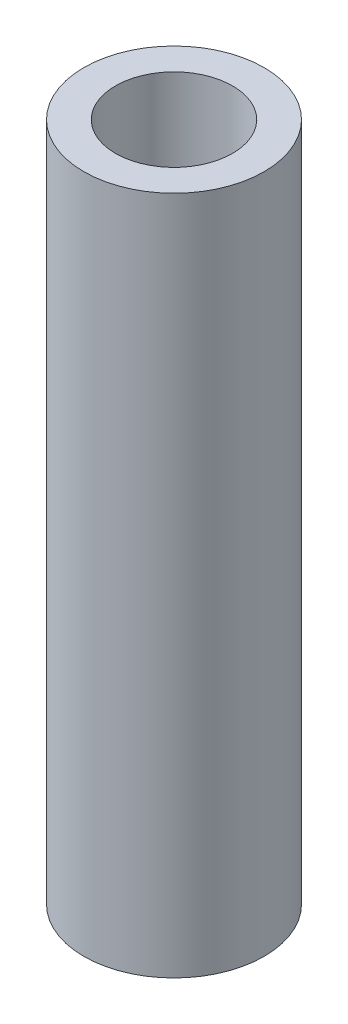
SolidWorks part; units mm, degrees
material "ABS"
ref_plane "Front Plane" through (0, 0, 0) normal (0, 0, 1) x (1, 0, 0)
ref_plane "Top Plane" through (0, 0, 0) normal (0, 1, 0) x (1, 0, 0)
ref_plane "Right Plane" through (0, 0, 0) normal (1, 0, 0) x (0, 0, -1)
sketch "Sketch1" plane through (0, 0, 0) normal (0, 1, 0) x (1, 0, 0)
  circle A0 centre (0, 0) radius 18.5
  circle A1 centre (0, 0) radius 28.5
  dimension "D1" = 37
  dimension "D2" = 57
extrude "Boss-Extrude1" add sketch "Sketch1" along normal blind 214.8
sketch "Sketch2" plane through (0, 0, 0) normal (1, 0, 0) x (0, 0, -1)
  line L0 (18.5, 214.8) -> (-18.5, 214.8) construction
  circle A0 centre (0, 150.1) radius 12.53
  circle A1 centre (0, 90.1) radius 12.53
  circle A2 centre (0, 30.1) radius 12.53
  dimension "D1" = 25.06
  dimension "D2" = 25.06
  dimension "D3" = 25.06
  dimension "D4" = 64.7
  dimension "D5" = 60
  dimension "D6" = 60
extrude "Cut-Extrude1" cut sketch "Sketch2" against normal through all
